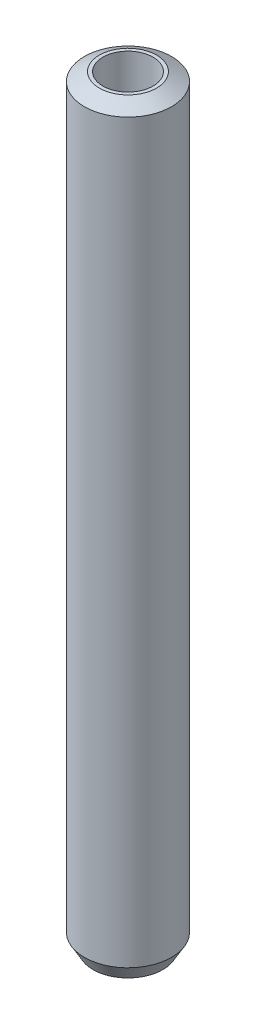
SolidWorks part; units mm, degrees
ref_plane "Front Plane" through (0, 0, 0) normal (0, 0, 1) x (1, 0, 0)
ref_plane "Top Plane" through (0, 0, 0) normal (0, 1, 0) x (1, 0, 0)
ref_plane "Right Plane" through (0, 0, 0) normal (1, 0, 0) x (0, 0, -1)
sketch "Sketch1" plane through (0, 0, 0) normal (0, 1, 0) x (1, 0, 0)
  circle A0 centre (0, 0) radius 22.5
  dimension "SHAFT_OD" = 45
extrude "Boss-Extrude1" add sketch "Sketch1" along normal blind 392.687
sketch "Sketch2" plane through (0, 0, 0) normal (0, 1, 0) x (1, 0, 0)
  circle A0 centre (0, 0) radius 12.9593
  dimension "BORE_D" = 25.9186
extrude "Cut-Extrude1" cut sketch "Sketch2" along normal through all
chamfer "Chamfer1" distance 4.4557 angle 60 2 edges at (0, 392.687, 22.5) (0, 0, 22.5) first distance on face at (0, 392.687, 22.5) first distance on face at (0, 0, 12.9593)
